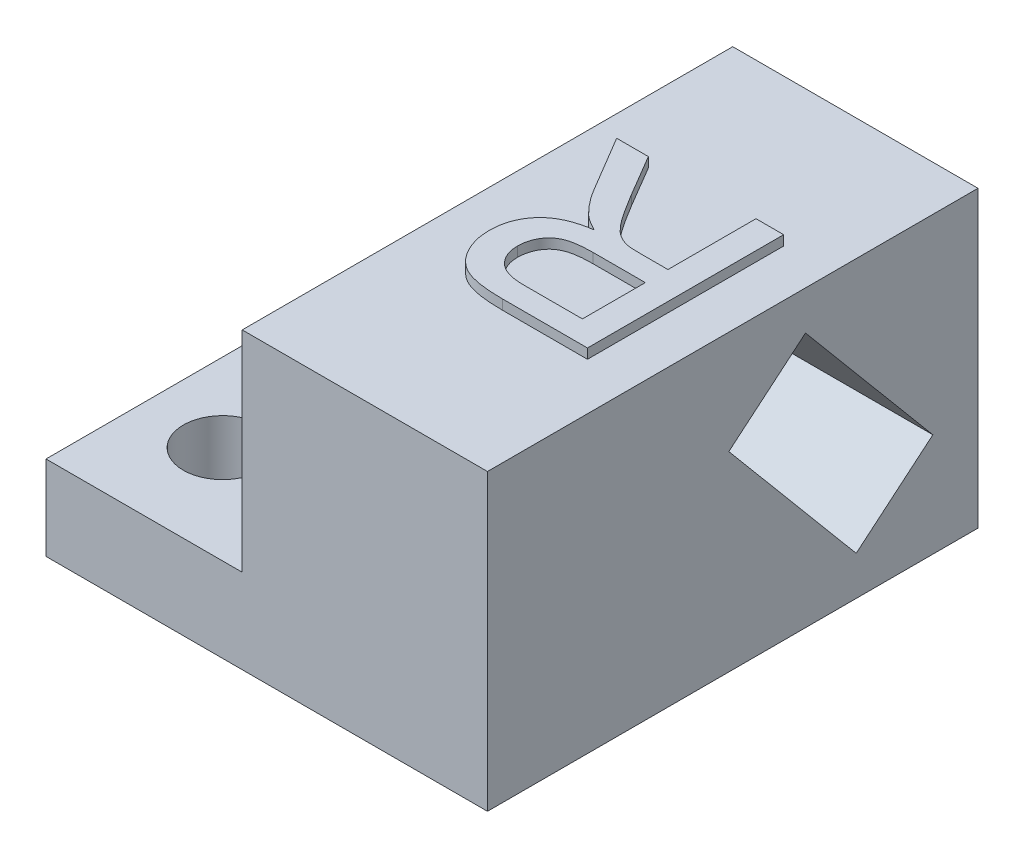
SolidWorks part; units mm, degrees
ref_plane "Спереди" through (0, 0, 0) normal (0, 0, 1) x (1, 0, 0)
ref_plane "Сверху" through (0, 0, 0) normal (0, 1, 0) x (1, 0, 0)
ref_plane "Справа" through (0, 0, 0) normal (1, 0, 0) x (0, 0, -1)
sketch "Sketch1" plane through (0, 0, 0) normal (0, 1, 0) x (1, 0, 0)
  line L1 (12.5, -25) -> (-12.5, -25)
  line L2 (12.5, -25) -> (12.5, 25)
  line L3 (12.5, 25) -> (-12.5, 25)
  line L4 (-12.5, -25) -> (-12.5, 25)
  line L5 (12.5, -25) -> (-12.5, 25) construction
  line L6 (12.5, 25) -> (-12.5, -25) construction
  point P0 (0, 0)
  dimension "D1" = 25
  dimension "D2" = 50
extrude "Boss-Extrude1" add sketch "Sketch1" along normal blind 30
sketch "Sketch2" plane through (-12.5, 0, 0) normal (-1, 0, 0) x (0, 0, 1)
  line L0 (-25, 4.3025) -> (25, 4.3025) construction
  line L1 (-25, 30) -> (-25, 0) construction
  line L2 (25, 30) -> (25, 0) construction
  line L4 (25, 8.605) -> (-25, 8.605)
  line L5 (25, 8.605) -> (25, 0)
  line L6 (25, 0) -> (-25, 0)
  line L7 (-25, 8.605) -> (-25, 0)
  line L8 (25, 8.605) -> (-25, 0) construction
  line L9 (25, 0) -> (-25, 8.605) construction
  point P6 (0, 4.3025)
extrude "Boss-Extrude2" add sketch "Sketch2" along normal blind 20
sketch "Sketch3" plane through (0, 8.605, 0) normal (0, 1, 0) x (1, 0, 0)
  line L0 (-24.5, -25) -> (-24.5, 25) construction
  line L1 (-32.5, 25) -> (-12.5, 25) construction
  line L2 (-32.5, -25) -> (-12.5, -25) construction
  circle A0 centre (-24.5, 15) radius 4
  circle A1 centre (-24.5, -15) radius 4
  dimension "D1" = 8
  dimension "D2" = 8
  dimension "D3" = 10
  dimension "D4" = 10
extrude "Cut-Extrude1" cut sketch "Sketch3" against normal through all
sketch "Sketch4" plane through (12.5, 0, 0) normal (1, 0, 0) x (0, 0, -1)
  line L0 (10, 30) -> (10, 0) construction
  line L1 (7.4147, 26.0153) -> (20.399, 10.5412)
  line L2 (7.4147, 26.0153) -> (-0.399, 19.4588)
  line L3 (-25, 30) -> (25, 30) construction
  line L4 (15.1, 4.9) -> (4.9, 4.9) construction
  line L5 (15.1, 4.9) -> (15.1, 25.1) construction
  line L6 (15.1, 25.1) -> (4.9, 25.1) construction
  line L7 (4.9, 4.9) -> (4.9, 25.1) construction
  line L8 (15.1, 4.9) -> (4.9, 25.1) construction
  line L9 (15.1, 25.1) -> (4.9, 4.9) construction
  line L10 (-25, 0) -> (25, 0) construction
  line L11 (25, 30) -> (25, 0) construction
  line L12 (20.399, 10.5412) -> (12.5853, 3.9847)
  line L13 (-0.399, 19.4588) -> (12.5853, 3.9847)
  line L14 (16.4922, 7.263) -> (3.5078, 22.737) construction
  line L15 (13.9068, 18.2782) -> (6.0932, 11.7218) construction
  point P6 (10, 15)
  point P11 (0, 0)
  point P12 (10, 15)
  point P13 (10, 15)
  dimension "D1" = 20.2
  dimension "D2" = 10.2
  dimension "D3" = 15
  dimension "D4" = 20.2
  dimension "D5" = 10.2
  dimension "D6" = 40
extrude "Cut-Extrude2" cut sketch "Sketch4" against normal blind 20
sketch "Sketch5" plane through (0, 30, 0) normal (0, 1, 0) x (1, 0, 0)
  line L0 (12.5, 10) -> (-12.5, 10) construction
  line L1 (12.5, -25) -> (12.5, 25) construction
  line L2 (-12.5, 25) -> (-12.5, -25) construction
  line L3 (12.5, 25) -> (-12.5, 25) construction
  text T0 "R" font "Arial" height 20
  dimension "D1" = 15
extrude "Boss-Extrude3" add sketch "Sketch5" along normal blind 1
